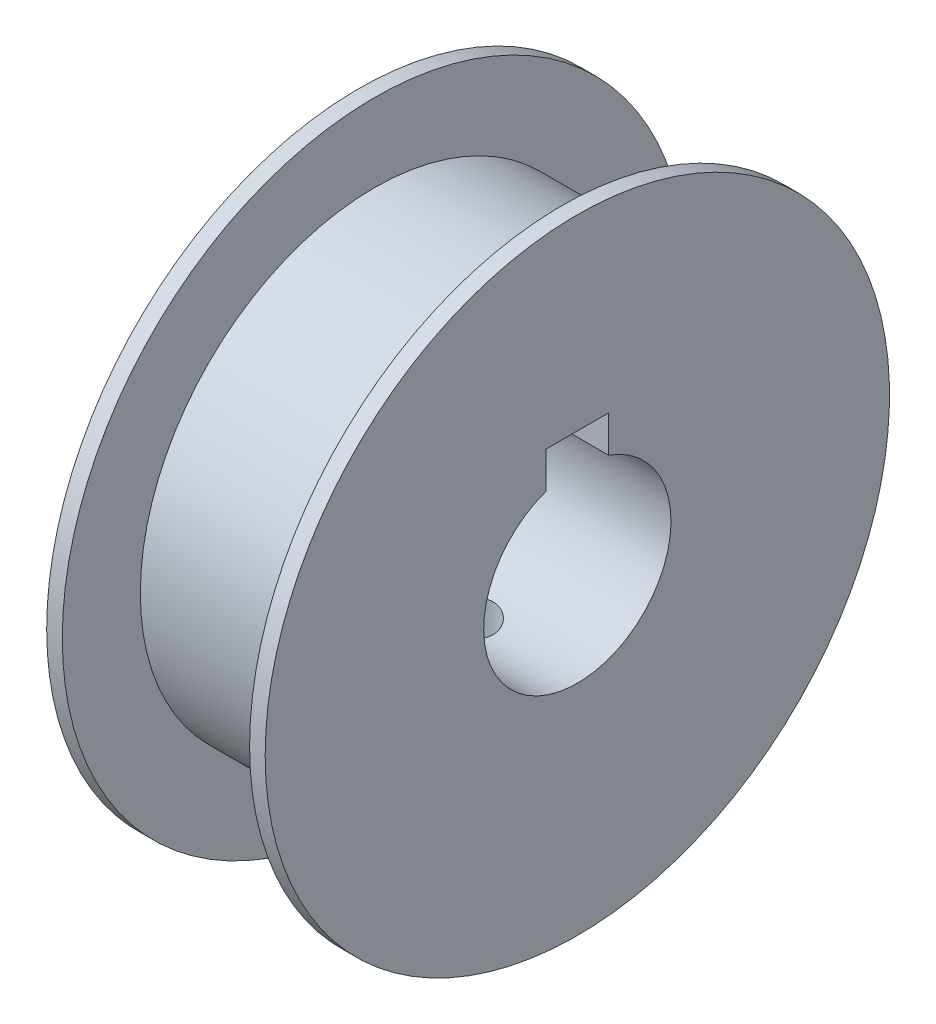
SolidWorks part; units mm, degrees
material "6061 合金"
ref_plane "正面" through (0, 0, 0) normal (0, 0, 1) x (1, 0, 0)
ref_plane "平面" through (0, 0, 0) normal (0, 1, 0) x (1, 0, 0)
ref_plane "右側面" through (0, 0, 0) normal (1, 0, 0) x (0, 0, -1)
sketch "ｽｹｯﾁ2" plane through (0, 0, 0) normal (0, 1, 0) x (1, 0, 0)
  line L0 (-44.7309, -0.056) -> (-44.7309, -14.056)
  line L1 (-44.7309, -0.056) -> (-43.7309, -0.056)
  line L2 (-43.7309, -0.056) -> (-43.7309, -5.056)
  line L3 (-43.7309, -5.056) -> (-31.7309, -5.056)
  line L4 (-31.7309, -5.056) -> (-31.7309, -0.056)
  line L5 (-31.7309, -0.056) -> (-30.7309, -0.056)
  line L6 (-30.7309, -0.056) -> (-30.7309, -14.056)
  line L7 (-30.7309, -14.056) -> (-44.7309, -14.056)
  line L8 (-49.8494, -20.056) -> (-18.0543, -20.056) construction
  dimension "D1" = 1
  dimension "D2" = 1
  dimension "D3" = 5
  dimension "D4" = 5
  dimension "D5" = 20
  dimension "D6" = 14
  dimension "D7" = 6
revolve "回転1" add sketch "ｽｹｯﾁ2" angle 360 about L8
sketch "ｽｹｯﾁ3" plane through (0, 0, 0) normal (0, 1, 0) x (1, 0, 0)
  line L1 (-43.7309, -0.056) -> (-44.7309, -0.056) construction
  line L2 (-30.7309, -40.056) -> (-30.7309, -0.056) construction
  circle A0 centre (-37.7309, -20.056) radius 1.6
  dimension "D1" = 3.2
  dimension "D2" = 20
  dimension "D3" = 7
extrude "ｶｯﾄ - 押し出し1" cut sketch "ｽｹｯﾁ3" against normal through all
sketch "ｽｹｯﾁ4" plane through (-30.7309, 0, 0) normal (1, 0, 0) x (0, 0, -1)
  line L1 (-22.056, 4) -> (-18.056, 4)
  line L2 (-22.056, 4) -> (-22.056, 8)
  line L3 (-22.056, 8) -> (-18.056, 8)
  line L4 (-18.056, 4) -> (-18.056, 8)
  line L5 (-22.056, 4) -> (-18.056, 8) construction
  line L6 (-22.056, 8) -> (-18.056, 4) construction
  circle A0 centre (-20.056, 0) radius 6 construction
  point P0 (-20.056, 6)
  dimension "D1" = 4
  dimension "D2" = 4
extrude "ｶｯﾄ - 押し出し2" cut sketch "ｽｹｯﾁ4" against normal through all
